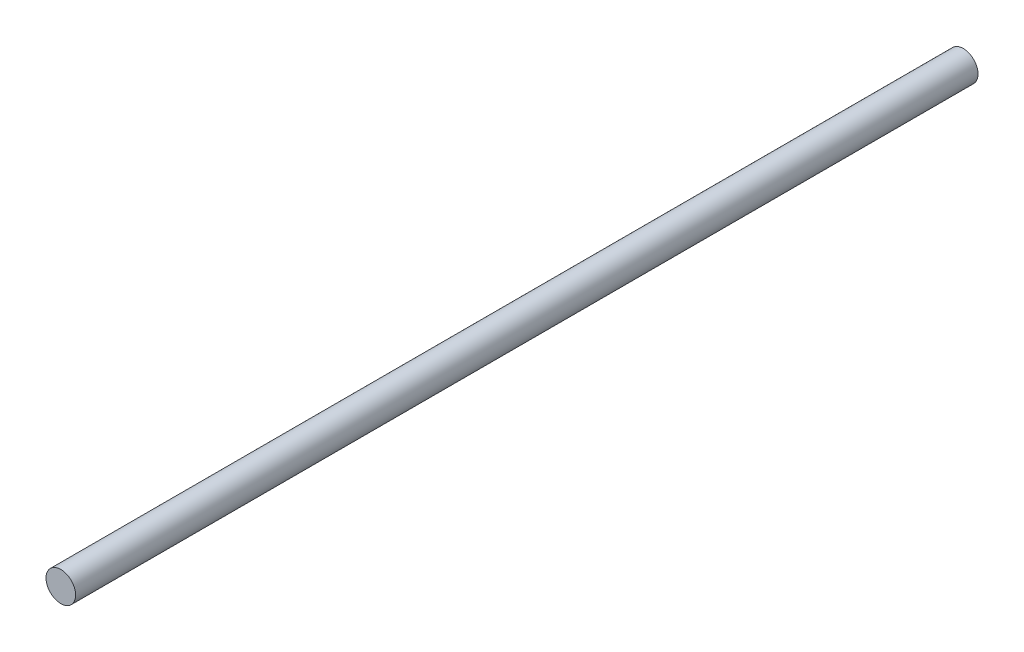
SolidWorks part; units mm, degrees
ref_plane "Front Plane" through (0, 0, 0) normal (0, 0, 1) x (1, 0, 0)
ref_plane "Top Plane" through (0, 0, 0) normal (0, 1, 0) x (1, 0, 0)
ref_plane "Right Plane" through (0, 0, 0) normal (1, 0, 0) x (0, 0, -1)
sketch "Sketch1" plane through (0, 0, 0) normal (0, 0, 1) x (1, 0, 0)
  circle A0 centre (0, 0) radius 2.5
extrude "Boss-Extrude1" add sketch "Sketch1" along normal blind 152.4
